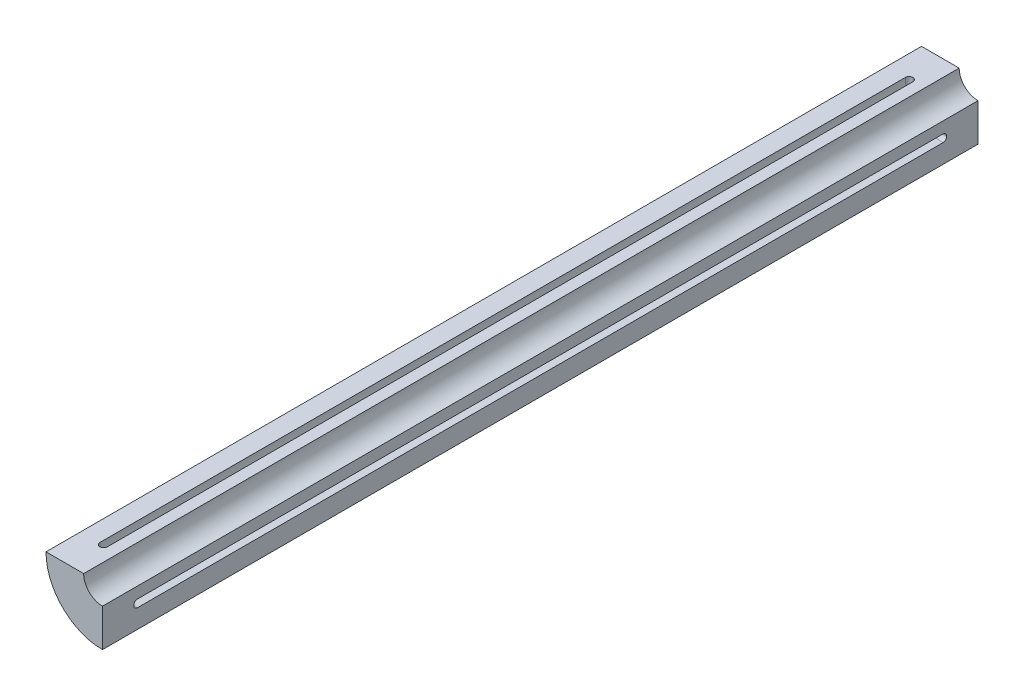
SolidWorks part; units mm, degrees
ref_plane "Front Plane" through (0, 0, 0) normal (0, 0, 1) x (1, 0, 0)
ref_plane "Top Plane" through (0, 0, 0) normal (0, 1, 0) x (1, 0, 0)
ref_plane "Right Plane" through (0, 0, 0) normal (1, 0, 0) x (0, 0, -1)
sketch "Sketch1" plane through (0, 0, 0) normal (0, 0, 1) x (1, 0, 0)
  line L0 (-5, 0.5035) -> (-8, 0.5035)
  line L5 (0, -4.4965) -> (0, -7.4965)
  line L6 (-10, 0.5035) -> (-15, 0.5035)
  line L7 (0, -9.4965) -> (0, -14.4965)
  arc A0 (-10, 0.5035) -> (0, -9.4965) centre (0, 0.5035) ccw
  arc A1 (-8, 0.5035) -> (0, -7.4965) centre (0, 0.5035) ccw
  arc A2 (-5, 0.5035) -> (0, -4.4965) centre (0, 0.5035) ccw
  arc A3 (-15, 0.5035) -> (0, -14.4965) centre (0, 0.5035) ccw
  dimension "D1" = 2
  dimension "D2" = 16
  dimension "D3" = 3
  dimension "D4" = 5
extrude "Boss-Extrude1" add sketch "Sketch1" along normal blind 215.9
sketch "Sketch2" plane through (0, 0, 215.9) normal (0, 0, 1) x (1, 0, 0)
  line L0 (-5, 0.5035) -> (-15, 0.5035)
  line L1 (0, -4.4965) -> (0, -14.4965)
  arc A0 (-5, 0.5035) -> (0, -4.4965) centre (0, 0.5035) ccw
  arc A1 (-5, 0.5035) -> (0, -4.4965) centre (0, 0.5035) ccw construction
  arc A2 (-15, 0.5035) -> (0, -14.4965) centre (0, 0.5035) ccw
extrude "Boss-Extrude2" add sketch "Sketch2" along normal blind 8.3
sketch "Sketch3" plane through (0, 0, 0) normal (0, 0, -1) x (-1, 0, 0)
  line L0 (5, 0.5035) -> (15, 0.5035)
  line L1 (0, -14.4965) -> (0, -4.4965)
  arc A0 (0, -4.4965) -> (5, 0.5035) centre (0, 0.5035) ccw
  arc A1 (15, 0.5035) -> (0, -14.4965) centre (0, 0.5035) cw
  arc A2 (0, -14.4965) -> (15, 0.5035) centre (0, 0.5035) ccw construction
  arc A3 (0, -4.4965) -> (5, 0.5035) centre (0, 0.5035) ccw construction
extrude "Boss-Extrude3" add sketch "Sketch3" along normal blind 8.3
fillet "Fillet1" radius 1 4 edges at (-5.6569, -5.1534, 0) (-7.0711, -6.5676, 0) (-5.6569, -5.1534, 215.9) (-7.0711, -6.5676, 215.9)
